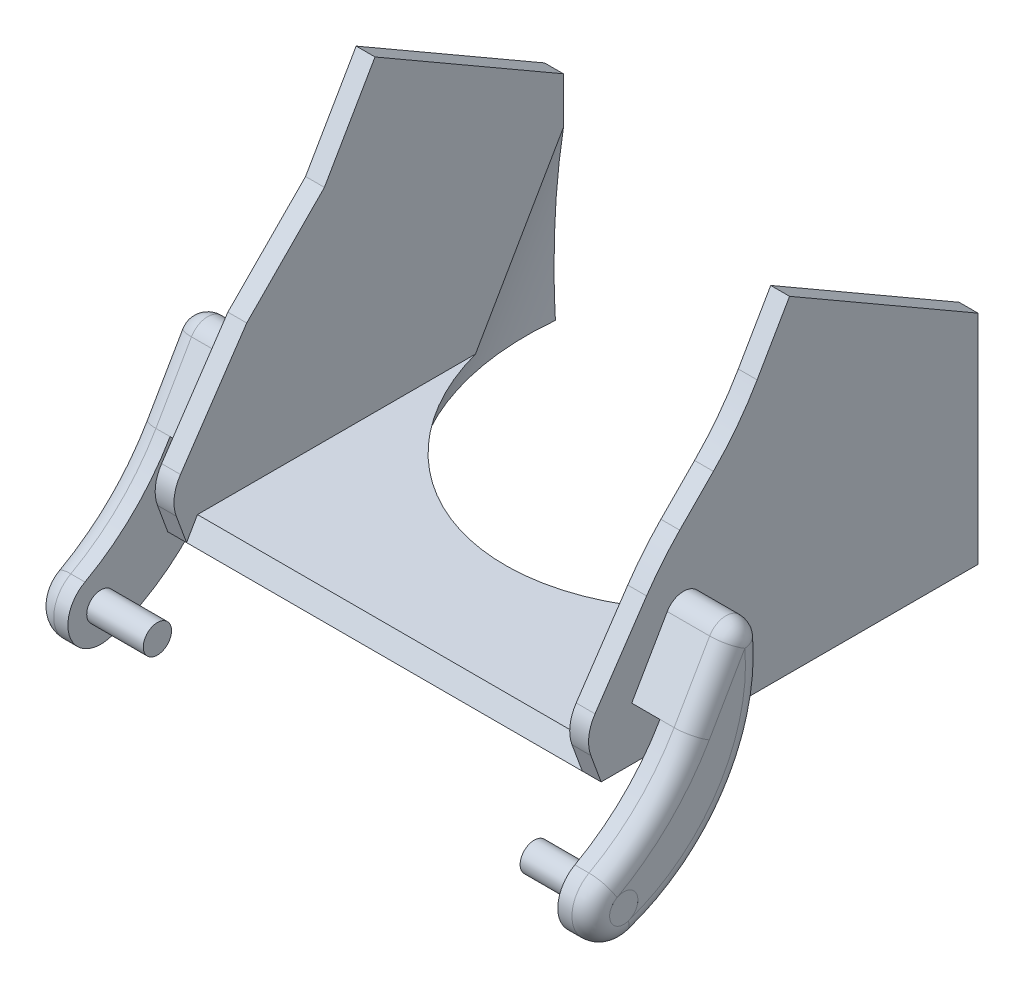
SolidWorks part; units mm, degrees
note: '?' marks a value the reader was unsure of. The reader was unsure of these and kept them because the rebuilt part matched: shared geometry of "Sketch5<4>".
ref_plane "Front Plane" through (0, 0, 0) normal (0, 0, 1) x (1, 0, 0)
ref_plane "Top Plane" through (0, 0, 0) normal (0, 1, 0) x (1, 0, 0)
ref_plane "Right Plane" through (0, 0, 0) normal (1, 0, 0) x (0, 0, -1)
sketch "Sketch1" plane through (0, 0, 0) normal (0, 0, 1) x (1, 0, 0)
  line L0 (-23, 40) -> (23, 40)
  line L1 (-23, 40) -> (-23, 0)
  line L2 (23, 40) -> (23, 0)
  line L3 (-23, 0) -> (23, 0)
  line L4 (-23, 40) -> (23, 0) construction
  line L5 (23, 40) -> (-23, 0) construction
  point P1 (0, 20)
  dimension "D1" = 40
  dimension "D2" = 46
extrude "Boss-Extrude1" add sketch "Sketch1" along normal blind 40
shell "Shell1" thickness 2 removed face at (0, 20, 0) removed face at (0, 20, 40) removed face at (0, 40, 20)
sketch "Sketch3" plane through (23, 0, 0) normal (1, 0, 0) x (0, 0, -1)
  line L0 (0, 0) -> (22.9751, -13.2647) construction
  line L1 (0, 0) -> (27.0489, 0) construction
  line L2 (0, 0) -> (10, 17.3205) construction
  dimension "D1" = 30
  dimension "D2" = 20
ref_plane "Plane1" through (0, 0, 0) normal (0, 0.866, -0.5) x (1, 0, 0)
sketch "Sketch2" plane through (0, 0, 0) normal (0, 0.866, -0.5) x (1, 0, 0)
  circle A0 centre (0, -2.5293) radius 22
  dimension "D1" = 44
extrude "Cut-Extrude1" cut sketch "Sketch2" against normal through all both and the other way through all contours A0
ref_plane "Plane2" through (0, 17.3205, 30) normal (0, 0.5, 0.866) x (1, 0, 0)
other "SurfaceCut1" flip cut yes
ref_plane "Plane4" through (0, 17.3205, -10) normal (0, 0.866, -0.5) x (1, 0, 0)
other "SurfaceCut3" flip cut yes
sketch "Sketch5" plane through (23, 0, 0) normal (1, 0, 0) x (0, 0, -1)
  line L0 (-35.6242, 7.5791) -> (-36.7529, 5.6242)
  line L1 (-30.4286, 16.5781) -> (-35.6242, 7.5791)
  line L4 (-40, 0) -> (0, 0) construction
  line L9 (-37, 0) -> (-41.5, -7.7942) construction
  line L10 (-41.5, -7.7942) -> (-44.0981, -6.2942) construction
  line L11 (-40, 0) -> (-20, 34.641) construction
  line L12 (-40, 0) -> (-37, 0) construction
  line L16 (-24.5, 26.8468) -> (-35.5, 7.7942) construction
  circle A0 centre (-44.0981, -6.2942) radius 1.5
  circle A1 centre (-44.0981, -6.2942) radius 3.5
  arc A3 (-36.7529, 5.6242) -> (-31.5928, 0) centre (-44.0981, -6.2942) cw construction
  arc A5 (-42.9839, -9.6121) -> (-30.4286, 16.5781) centre (-49.4298, 9.5825) ccw
  arc A6 (-45.7864, -3.2283) -> (-36.7529, 5.6242) centre (-57.1444, 17.3972) ccw
  dimension "D1" = 3
  dimension "D2" = 2
  dimension "D3" = 3
  dimension "D6" = 14
  dimension "D4" = 9
  dimension "D5" = 3
extrude "Boss-Extrude2" add sketch "Sketch5" along normal blind 6.5
ref_axis "Axis1" through (29.5, -6.2942, 44.0981) along (-1, 0, 0)?
sketch "Sketch7" plane through (23, 0, 0) normal (1, 0, 0) x (0, 0, -1)
  line L0 (-40, 0) -> (-41.0897, 2.9692)
  line L1 (-24.5, 26.8468) -> (-35.5, 7.7942) construction
  line L2 (-40.6489, 6.587) -> (-33.6152, 16.9955)
  line L3 (-33.6152, 16.9955) -> (-25.3707, 25.3386)
  line L4 (-30.4286, 16.5781) -> (-20, 34.641) construction
  line L5 (-30.4286, 16.5781) -> (-20, 34.641) construction
  line L6 (-40, 0) -> (-25.3707, 25.3386)
  arc A0 (-41.0897, 2.9692) -> (-40.6489, 6.587) centre (-37.3346, 4.3474) cw
  point P17 (-41.795, 4.8909)
  line M5 (-20, 34.641) -> (-30.4286, 16.5781)
  dimension "D2" = 4
  dimension "D1" = 4
extrude "Boss-Extrude4" add sketch "Sketch7" against normal blind 2 contours L3 L2 L0 M5
ref_plane "Plane5" through (0, -23.8157, 13.75) normal (0, 0.866, -0.5) x (-1, 0, 0)
sketch "Sketch6" plane through (0, -27.5, 7.3686) normal (0, 0.866, -0.5) x (1, 0, 0)
  line L0 (23, -42.0096) -> (23, -18.9156) construction
  line L1 (23, -42.4115) -> (26, -42.4115)
  line L2 (23, -42.4115) -> (23, -28.4115)
  line L3 (23, -28.4115) -> (26, -28.4115)
  line L4 (26, -42.4115) -> (26, -28.4115)
  line L5 (29.5, -43.9115) -> (29.5, -40.9115) construction
  line L6 (29.5, -43.9115) -> (29.5, -40.9115)
  point P8 (29.5, -42.4115)
  dimension "D1" = 3
  dimension "D2" = 14
revolve "Cut-Revolve1" cut sketch "Sketch6" angle 360 about L1
fillet "Fillet1" radius 30 2 edges at (22, 25.3386, 25.3707) (22, 16.9955, 33.6152)
fillet "Fillet2" radius 2 5 edges at (26.25, 16.5781, 30.4286) (29.5, 0.58, 40.6641) (29.5, 0.8297, 31.1713) (29.5, 11.1012, 33.5907) (29.5, -7.7011, 47.3029)
extrude "Boss-Extrude5" add sketch "Sketch5<4>" along normal up to surface (6.5 mm away) and the other way blind 6 from surface at 3 separate body contours A0 starting at face at (26, -6.2942, 45.5981)
sketch "Sketch5<4>" plane through (23, 0, 0) normal (1, 0, 0) x (0, 0, -1) same geometry as "Sketch5"
mirror "Mirror2" about plane through (0, 0, 0) normal (1, 0, 0) of "Boss-Extrude4", "Cut-Revolve1", "Boss-Extrude2", "Fillet2"
mirror "Mirror4" about plane through (0, 0, 0) normal (1, 0, 0) of bodies 121
equation "\"in_d\"=40"
equation "\"pipe_thick\"=2"
equation "\"rod_angle\"=20"
equation "\"rod_radius\"=33.5"
equation "\"rod_diameter\"=8"
equation "\"lin_bear_h\"=24"
equation "\"screw_radius\"=40"
equation "\"screw_angle\"=50"
equation "\"lin_bearing_d\"=15"
equation "\"drill_rod_pair\"=37"
equation "\"support_rod_w\"=50"
equation "\"vertical_slider_w\"=65"
equation "\"D1@Sketch2\"=\"in_d\"+2*\"pipe_thick\""
equation "\"slope_angle\"=30"
equation "\"D1@Sketch3\"=\"slope_angle\""
equation "\"D2@Sketch1\"=\"in_d\"+2*\"pipe_thick\"+2"
